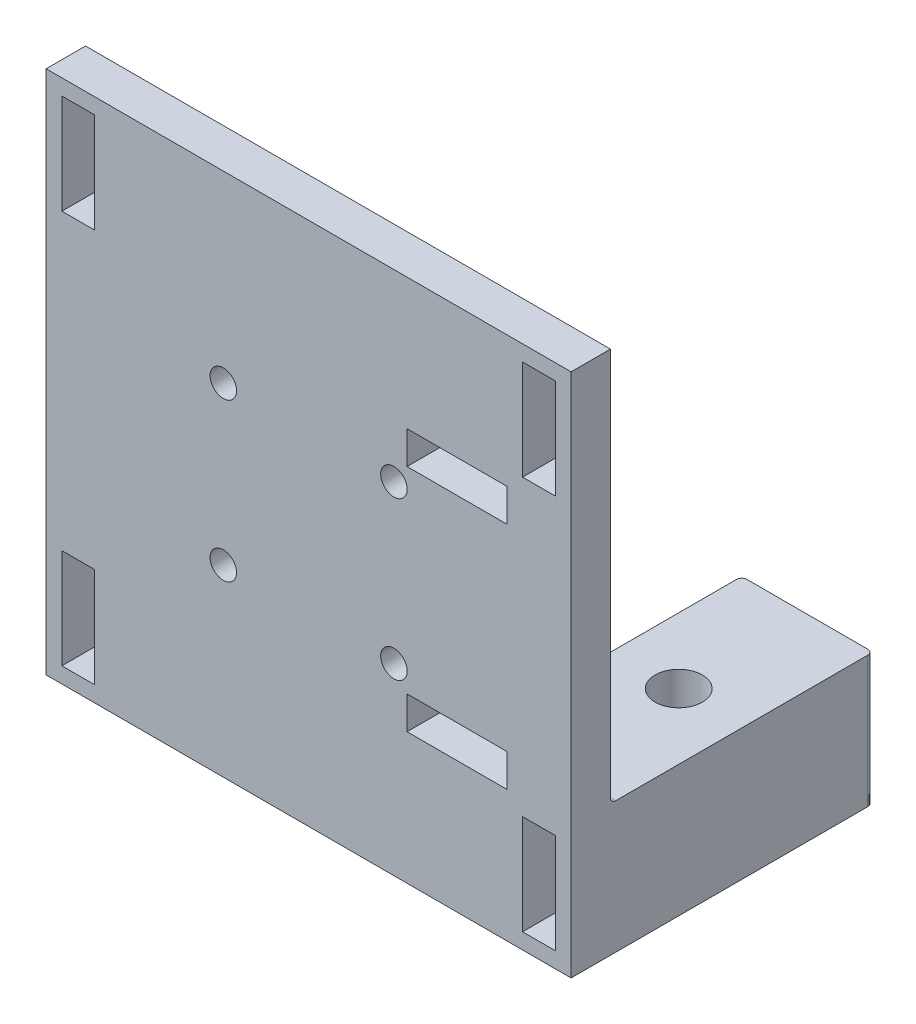
SolidWorks part; units mm, degrees
material "PET"
ref_plane "Alzado" through (0, 0, 0) normal (0, 0, 1) x (1, 0, 0)
ref_plane "Planta" through (0, 0, 0) normal (0, 1, 0) x (1, 0, 0)
ref_plane "Vista lateral" through (0, 0, 0) normal (1, 0, 0) x (0, 0, -1)
sketch "Sketch1" plane through (0, 0, 0) normal (0, 0, 1) x (1, 0, 0)
  line L0 (0, -1000) -> (0, 49000) construction
  line L5 (-1000, 0) -> (49000, 0) construction
  line L7 (-20, -20) -> (20, -20)
  line L8 (-20, -20) -> (-20, 20)
  line L9 (-20, 20) -> (20, 20)
  line L10 (20, -20) -> (20, 20)
  line L11 (-20, -20) -> (20, 20) construction
  line L12 (-20, 20) -> (20, -20) construction
  circle A0 centre (6.5, -6) radius 1.01
  circle A1 centre (-6.5, -6) radius 1.01
  circle A2 centre (6.5, 6) radius 1.01
  circle A3 centre (-6.5, 6) radius 1.01
  point P14 (0, 0)
  dimension "D3" = 2.02
  dimension "D1" = 6
  dimension "D2" = 6.5
  dimension "D4" = 40
  dimension "D5" = 40
extrude "Boss-Extrude1" add sketch "Sketch1" along normal blind 3
sketch "Sketch4" plane through (0, 0, 0) normal (0, 0, -1) x (-1, 0, 0)
  line L0 (20, 20) -> (20, -20) construction
  line L1 (-20, -20) -> (20, -20)
  line L2 (-20, -20) -> (-20, -10)
  line L3 (-20, -10) -> (20, -10)
  line L4 (20, -20) -> (20, -10)
  dimension "D1" = 10
extrude "Boss-Extrude2" add sketch "Sketch4" along normal blind 20
fillet "Fillet1" radius 0.4 1 edges at (0, -10, 0)
sketch "Sketch5" plane through (0, -10, 0) normal (0, 1, 0) x (1, 0, 0)
  line L0 (-20, 0.4) -> (20, 0.4) construction
  line L1 (-10, 20) -> (10, 20)
  line L2 (-10, 20) -> (-10, 0.4)
  line L3 (-10, 0.4) -> (10, 0.4)
  line L4 (10, 20) -> (10, 0.4)
  line L5 (-10, 20) -> (10, 0.4) construction
  line L6 (-10, 0.4) -> (10, 20) construction
  line L7 (-20, 20) -> (20, 20) construction
  line L8 (0, 20) -> (0, 0.4) construction
  line L9 (20, 20) -> (10, 0.4) construction
  circle A0 centre (15, 10.2) radius 1.8
  circle A1 centre (-15, 10.2) radius 1.8
  point P0 (0, 10.2)
  point P17 (15, 10.2)
  dimension "D2" = 3.6
  dimension "D1" = 20
extrude "Cut-Extrude2" cut sketch "Sketch5" against normal through all
sketch "Sketch2" plane through (0, 0, 3) normal (0, 0, 1) x (1, 0, 0)
  line L0 (0, 20) -> (0, -20) construction
  line L1 (20, 20) -> (-20, 20) construction
  line L2 (-20, -20) -> (20, -20) construction
  line L3 (-20, 0) -> (20, 0) construction
  line L4 (-20, 20) -> (-20, -20) construction
  line L5 (20, -20) -> (20, 20) construction
  line L6 (18.8, 11.2) -> (16.3, 11.2)
  line L7 (-18.8, 18.8) -> (-16.3, 18.8)
  line L8 (-18.8, 18.8) -> (-18.8, 11.2)
  line L9 (-18.8, 11.2) -> (-16.3, 11.2)
  line L10 (-16.3, 18.8) -> (-16.3, 11.2)
  line L23 (7.5, 10) -> (15.1, 10)
  line L24 (7.5, 10) -> (7.5, 7.5)
  line L25 (7.5, 7.5) -> (15.1, 7.5)
  line L26 (15.1, 10) -> (15.1, 7.5)
  line L31 (18.8, 18.8) -> (18.8, 11.2)
  line L32 (18.8, 18.8) -> (16.3, 18.8)
  line L33 (16.3, 18.8) -> (16.3, 11.2)
  line L34 (16.3, -18.8) -> (16.3, -11.2)
  line L35 (18.8, -18.8) -> (16.3, -18.8)
  line L36 (18.8, -18.8) -> (18.8, -11.2)
  line L37 (18.8, -11.2) -> (16.3, -11.2)
  line L38 (-18.8, -11.2) -> (-16.3, -11.2)
  line L39 (-18.8, -18.8) -> (-18.8, -11.2)
  line L40 (-18.8, -18.8) -> (-16.3, -18.8)
  line L41 (-16.3, -18.8) -> (-16.3, -11.2)
  line L42 (15.1, -10) -> (15.1, -7.5)
  line L43 (7.5, -7.5) -> (15.1, -7.5)
  line L44 (7.5, -10) -> (7.5, -7.5)
  line L45 (7.5, -10) -> (15.1, -10)
  point P36 (15.1, 8.75)
  dimension "D1" = 7.6
  dimension "D2" = 2.5
  dimension "D3" = 1.2
  dimension "D4" = 1.2
  dimension "D5" = 2.5
  dimension "D6" = 7.6
  dimension "D7" = 1.2
  dimension "D8" = 1.2
extrude "Cut-Extrude1" cut sketch "Sketch2" against normal through all
fillet "Fillet2" radius 0.4 6 edges at (-10, -15, -0.4) (10, -15, -0.4) (-10, -15, -20) (-20, -15, -20) (20, -15, -20) (10, -15, -20)
